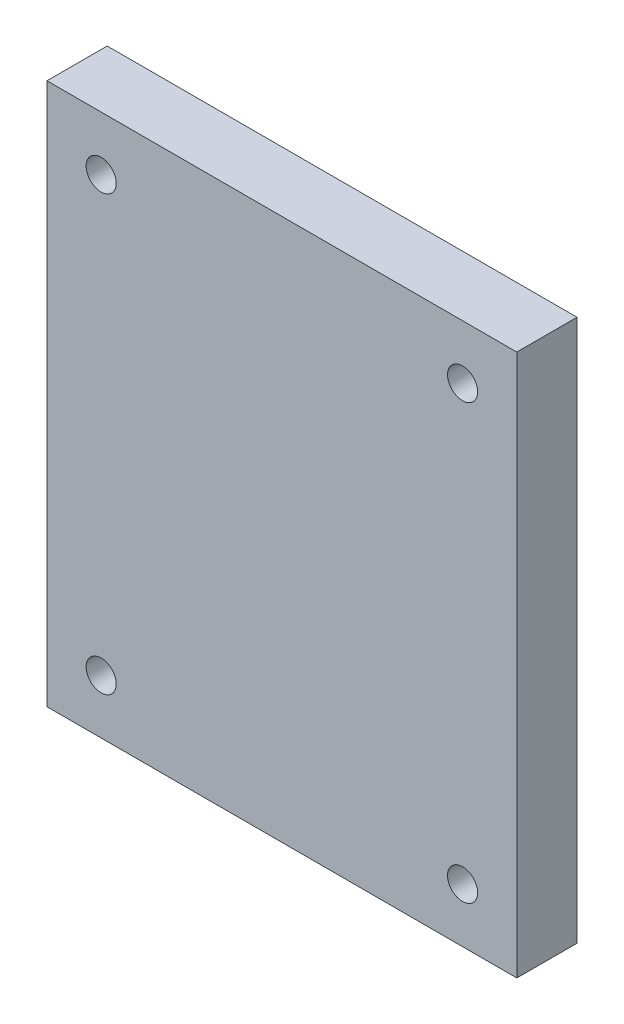
SolidWorks part; units mm, degrees
ref_plane "Front Plane" through (0, 0, 0) normal (0, 0, 1) x (1, 0, 0)
ref_plane "Top Plane" through (0, 0, 0) normal (0, 1, 0) x (1, 0, 0)
ref_plane "Right Plane" through (0, 0, 0) normal (1, 0, 0) x (0, 0, -1)
sketch "Sketch1" plane through (0, 0, 0) normal (0, 0, 1) x (1, 0, 0)
  line L0 (0, -1000) -> (0, 49000) construction
  line L1 (-19.5, 22.5) -> (19.5, 22.5)
  line L2 (-19.5, 22.5) -> (-19.5, -22.5)
  line L3 (-19.5, -22.5) -> (19.5, -22.5)
  line L4 (19.5, 22.5) -> (19.5, -22.5)
  line L5 (-1000, 0) -> (49000, 0) construction
  circle A0 centre (-15, 18) radius 1.25
  circle A1 centre (15, 18) radius 1.25
  circle A2 centre (15, -18) radius 1.25
  circle A3 centre (-15, -18) radius 1.25
  dimension "D1" = 2.5
extrude "Boss-Extrude1" add sketch "Sketch1" along normal blind 5
